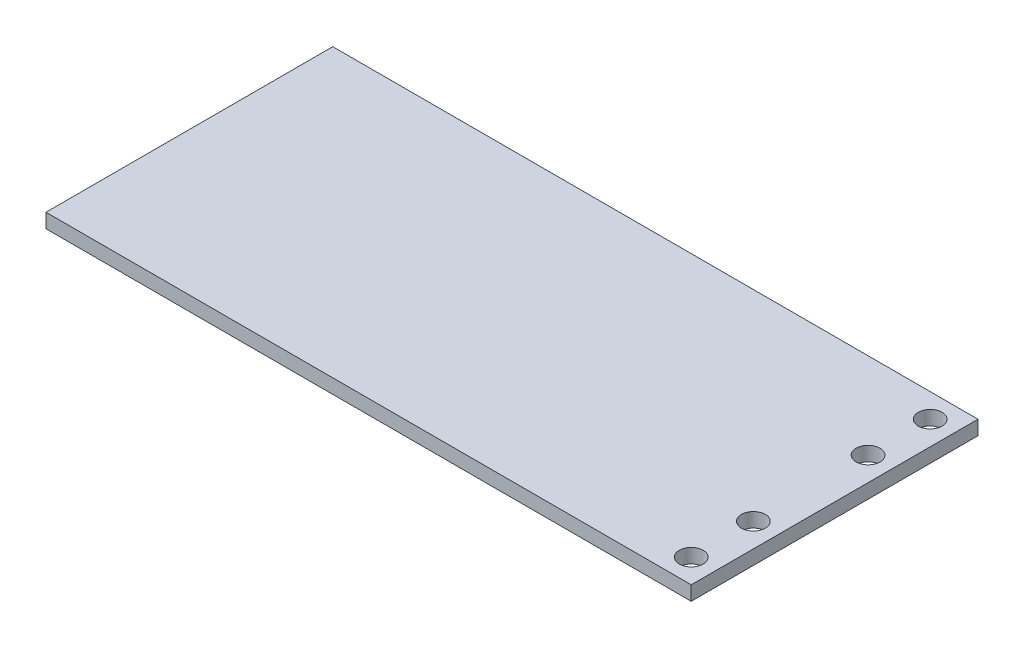
SolidWorks part; units mm, degrees
ref_plane "Front Plane" through (0, 0, 0) normal (0, 0, 1) x (1, 0, 0)
ref_plane "Top Plane" through (0, 0, 0) normal (0, 1, 0) x (1, 0, 0)
ref_plane "Right Plane" through (0, 0, 0) normal (1, 0, 0) x (0, 0, -1)
sketch "Sketch1" plane through (0, 0, 0) normal (0, 1, 0) x (1, 0, 0)
  line L0 (130, 60) -> (130, 0) construction
  line L1 (0, 0) -> (135, 0)
  line L2 (0, 0) -> (0, 60)
  line L3 (0, 60) -> (135, 60)
  line L4 (135, 0) -> (135, 60)
  circle A0 centre (130, 42) radius 2.5
  circle A2 centre (130, 18) radius 2.5
  circle A3 centre (130, 5) radius 2.5
  circle A4 centre (130, 55) radius 2.5
  point P15 (130, 44.5)
  point P17 (130, 7.5)
  dimension "D8" = 5
  dimension "D1" = 135
  dimension "D2" = 60
  dimension "D3" = 5
  dimension "D4" = 18
  dimension "D5" = 5
  dimension "D6" = 13
  dimension "D7" = 5
extrude "Boss-Extrude1" add sketch "Sketch1" along normal blind 3 contours L0 L3 L2 L1 A3 A2 A0 A4 | L3 L0 A4 A0 A2 A3 L1 L4 region at (132.7167, 0, -30) region at (64.6765, 0, -30)
sketch "Sketch2" plane through (0, 3, 0) normal (0, 1, 0) x (1, 0, 0)
  line L1 (50, 19.5563) -> (85, 19.5563)
  line L2 (50, 19.5563) -> (50, 54.5563)
  line L3 (50, 54.5563) -> (85, 54.5563)
  line L4 (85, 19.5563) -> (85, 54.5563)
  line L6 (67.5, 60) -> (67.5, 54.5563) construction
  line L7 (0, 60) -> (135, 60) construction
  point P11 (67.5, 54.5563)
  point P18 (67.5, 60)
  dimension "D2" = 35
